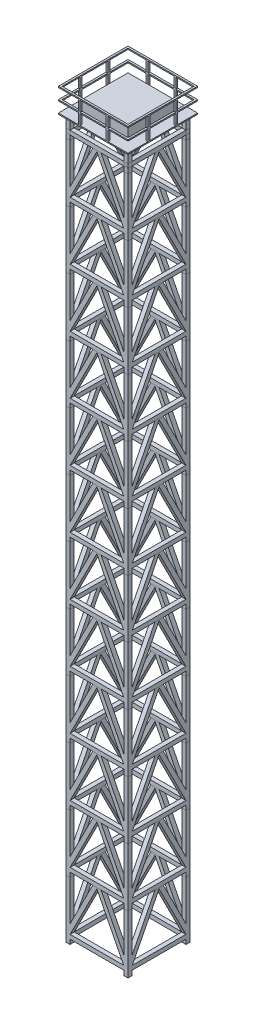
SolidWorks part; units mm, degrees
note: '?' marks a value the reader was unsure of.
ref_plane "Front Plane" through (0, 0, 0) normal (0, 0, 1) x (1, 0, 0)
ref_plane "Top Plane" through (0, 0, 0) normal (0, 1, 0) x (1, 0, 0)
ref_plane "Right Plane" through (0, 0, 0) normal (1, 0, 0) x (0, 0, -1)
sketch "Sketch1" plane through (0, 0, 0) normal (0, 1, 0) x (1, 0, 0)
  line L1 (1160, -1340) -> (1340, -1340)
  line L2 (1160, -1340) -> (1160, -1160)
  line L3 (1160, -1160) -> (1340, -1160)
  line L4 (1340, -1340) -> (1340, -1160)
  line L5 (1160, -1340) -> (1340, -1160) construction
  line L6 (1160, -1160) -> (1340, -1340) construction
  point P0 (1250, -1250)
  dimension "D1" = 1250
  dimension "D2" = 1250
  dimension "D3" = 180
  dimension "D4" = 180
extrude "Boss-Extrude1" add sketch "Sketch1" along normal blind 2500
sketch "Sketch2" plane through (1160, 0, 0) normal (-1, 0, 0) x (0, 0, 1)
  line L0 (1340, 2500) -> (1340, 0) construction
  line L1 (1340, 380) -> (1160, 380)
  line L2 (1340, 380) -> (1340, 200)
  line L3 (1340, 200) -> (1160, 200)
  line L4 (1160, 380) -> (1160, 200)
  line L5 (1160, 2500) -> (1160, 0) construction
  line L6 (1160, 0) -> (1340, 0) construction
  point P11 (1250, 200)
  dimension "D1" = 180
  dimension "D2" = 200
extrude "Boss-Extrude2" add sketch "Sketch2" along normal blind 2320
ref_axis "Axis1" through (0, 0, 0) along (0, 1, 0)?
ref_plane "Plane1" through (0, 0, 1340) normal (0, 0, 1) x (1, 0, 0)
sketch "Sketch3" plane through (0, 0, 1340) normal (0, 0, 1) x (1, 0, 0)
  line L0 (1181.6443, 325.258) -> (0, 2656.9642)
  line L3 (179.9849, 2700) -> (1181.6443, 723.453)
  line L5 (1181.6443, 723.453) -> (1181.6443, 325.258)
  line L11 (0, -99) -> (0, 99) construction
  line L12 (179.9849, 2700) -> (0, 2700)
  line L13 (0, 2700) -> (0, 2656.9642)
  line L14 (1340, 2500) -> (1160, 2500) construction
  dimension "D1" = 200
  dimension "D2" = 180
extrude "Boss-Extrude3" add sketch "Sketch3" against normal up to surface (180 mm away) up to face at (625, 770, 1160)
mirror "Mirror2" about plane through (0, 0, 0) normal (1, 0, 0) of "Boss-Extrude3"
pattern_circular "CirPattern4" count 4 over 360 about axis through (0, 0, 0) along (0, 1, 0) of bodies 108
combine bodies "Combine1" bodies to combine 108 109 110 111
pattern_linear "LPattern1" count 12 spacing 2500 along (0, 1, 0) of bodies 112
sketch "Sketch4" plane through (0, 30000, 0) normal (0, 1, 0) x (1, 0, 0)
  line L1 (1340, -1160) -> (1160, -1160)
  line L2 (1340, -1160) -> (1340, -1340)
  line L3 (1340, -1340) -> (1160, -1340)
  line L4 (1160, -1160) -> (1160, -1340)
extrude "Boss-Extrude4" add sketch "Sketch4" along normal up to surface (200 mm away) separate body
sketch "Sketch5" plane through (0, 30200, 0) normal (0, 1, 0) x (1, 0, 0)
  line L0 (-1340, -1160) -> (-1340, -1340) construction
  line L5 (1340, -1340) -> (-1340, -1340)
  line L6 (1340, -1340) -> (1340, -1160)
  line L7 (1340, -1160) -> (-1340, -1160)
  line L8 (-1340, -1340) -> (-1340, -1160)
  line L9 (-1160, -1160) -> (-1340, -1160) construction
extrude "Boss-Extrude5" add sketch "Sketch5" along normal blind 180 separate body
sketch "Sketch6" plane through (0, 30380, 0) normal (0, 1, 0) x (1, 0, 0)
  line L0 (1340, -1160) -> (-1340, -1160) construction
  line L1 (1340, -1340) -> (1160, -1340)
  line L2 (1340, -1340) -> (1340, -1160)
  line L3 (1340, -1160) -> (1160, -1160)
  line L4 (1160, -1340) -> (1160, -1160)
  dimension "D1" = 180
extrude "Boss-Extrude6" add sketch "Sketch6" along normal blind 500 separate body
pattern_circular "CirPattern8" count 4 over 360 about axis through (0, 0, 0) along (0, 1, 0) of bodies 125 124 126
sketch "Sketch7" plane through (0, 30880, 0) normal (0, 1, 0) x (1, 0, 0)
  line L1 (-1500, 1500) -> (1500, 1500)
  line L2 (-1500, 1500) -> (-1500, -1500)
  line L3 (-1500, -1500) -> (1500, -1500)
  line L4 (1500, 1500) -> (1500, -1500)
  line L5 (-1500, 1500) -> (1500, -1500) construction
  line L6 (-1500, -1500) -> (1500, 1500) construction
  point P0 (0, 0)
extrude "Boss-Extrude7" add sketch "Sketch7" along normal blind 50
sketch "Sketch8" plane through (0, 30930, 0) normal (0, 1, 0) x (1, 0, 0)
  line L1 (1000, -1000) -> (-1000, -1000)
  line L2 (1000, -1000) -> (1000, 1000)
  line L3 (1000, 1000) -> (-1000, 1000)
  line L4 (-1000, -1000) -> (-1000, 1000)
  line L5 (1000, -1000) -> (-1000, 1000) construction
  line L6 (1000, 1000) -> (-1000, -1000) construction
  point P0 (0, 0)
  dimension "D1" = 2000
  dimension "D2" = 2000
extrude "Boss-Extrude8" add sketch "Sketch8" along normal blind 500
sketch "Sketch9" plane through (0, 30930, 0) normal (0, 1, 0) x (1, 0, 0)
  line L0 (1500, -1500) -> (1500, 1500) construction
  line L1 (1420, -640) -> (1500, -640)
  line L2 (1420, -640) -> (1420, -560)
  line L3 (1420, -560) -> (1500, -560)
  line L4 (1500, -640) -> (1500, -560)
  line L5 (1420, -640) -> (1500, -560) construction
  line L6 (1420, -560) -> (1500, -640) construction
  line L7 (-1650, 0) -> (1650, 0) construction
  point P0 (1460, -600)
  dimension "D1" = 80
  dimension "D2" = 80
extrude "Boss-Extrude9" add sketch "Sketch9" along normal blind 1000
mirror "Mirror3" about plane through (0, 0, 0) normal (0, 0, 1) of "Boss-Extrude9"
sketch "Sketch10" plane through (0, 31930, 0) normal (0, 1, 0) x (1, 0, 0)
  line L0 (-1500, -1500) -> (1500, -1500) construction
  line L1 (1420, -1500) -> (1500, -1500)
  line L2 (1420, -1500) -> (1420, 1500)
  line L3 (1420, 1500) -> (1500, 1500)
  line L4 (1500, -1500) -> (1500, 1500)
extrude "Boss-Extrude10" add sketch "Sketch10" against normal blind 50
pattern_linear "LPattern2" count 2 spacing 500 along (0, -1, 0) of "Boss-Extrude10"
pattern_circular "CirPattern9" count 4 over 360 about axis through (0, 0, 0) along (0, 1, 0) of "LPattern2", "Boss-Extrude10", "Boss-Extrude9", "Mirror3"
equation "\"D2@Sketch1\"=\"D1@Sketch1\""
equation "\"D4@Sketch1\"=\"D3@Sketch1\""
equation "\"D1@Sketch2\"=\"D3@Sketch1\""
equation "\"D2@Sketch7\"=\"D1@Sketch7\""
equation "\"D2@Sketch8\"=\"D1@Sketch8\""
equation "\"D2@Sketch9\"=\"D1@Sketch9\""
